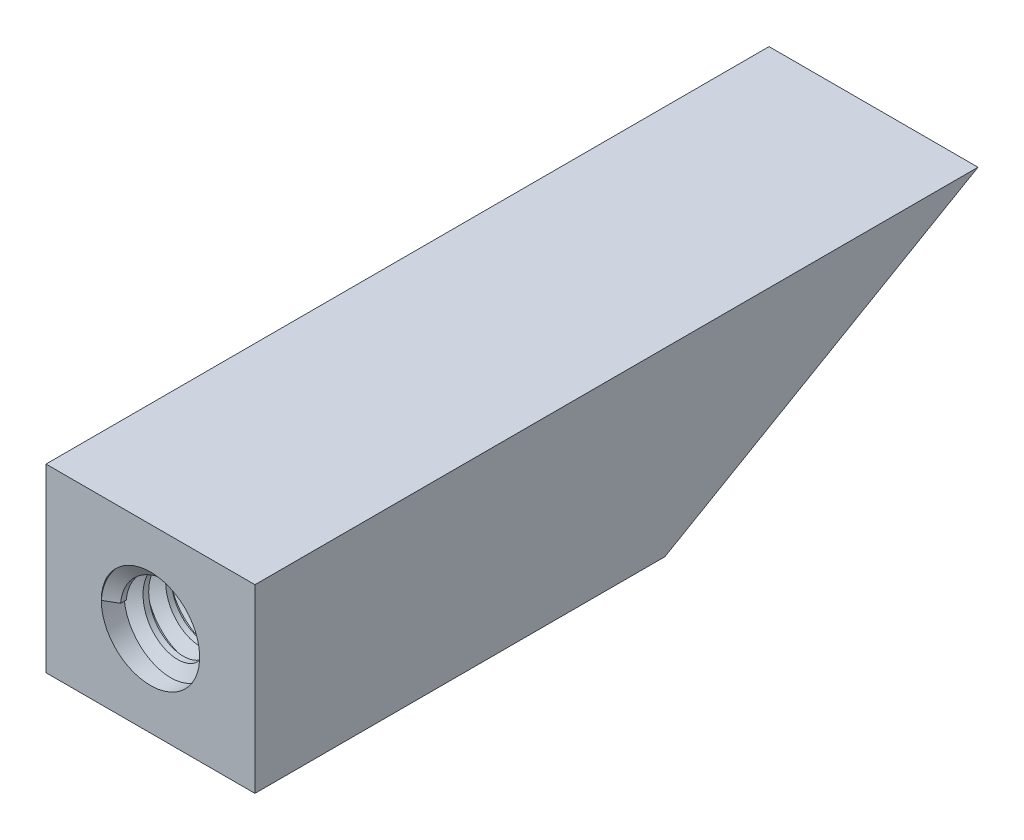
SolidWorks part; units mm, degrees
ref_plane "Front Plane" through (0, 0, 0) normal (0, 0, 1) x (1, 0, 0)
ref_plane "Top Plane" through (0, 0, 0) normal (0, 1, 0) x (1, 0, 0)
ref_plane "Right Plane" through (0, 0, 0) normal (1, 0, 0) x (0, 0, -1)
sketch "Sketch1" plane through (0, 0, 0) normal (0, 0, 1) x (1, 0, 0)
  line L1 (-3.6703, -3.175) -> (3.6703, -3.175)
  line L2 (-3.6703, -3.175) -> (-3.6703, 3.175)
  line L3 (-3.6703, 3.175) -> (3.6703, 3.175)
  line L4 (3.6703, -3.175) -> (3.6703, 3.175)
  line L5 (-3.6703, -3.175) -> (3.6703, 3.175) construction
  line L6 (-3.6703, 3.175) -> (3.6703, -3.175) construction
  point P0 (0, 0)
  dimension "D1" = 6.35
  dimension "D2" = 7.3406
extrude "Boss-Extrude1" add sketch "Sketch1" along normal blind 25.4
sketch "Sketch3" plane through (0, 0, 25.4) normal (0, 0, 1) x (1, 0, 0)
  line L0 (-3.6703, 3.175) -> (3.6703, -3.175) construction
  circle A0 centre (0, 0) radius 1.7272
  dimension "D1" = 3.4544
extrude "Cut-Extrude2" cut sketch "Sketch3" against normal blind 25.4
thread "Thread1" pitch 0.7937 method extrude profile "Thread Profile3" start angle 0, offset 0, length 25.4, pitch 0.7937, diameter 3.4544
ref_plane "Plane3" through (-1.7272, 0, 25.4) normal (0, -1, 0) x (-1, 0, 0)
sketch "Thread Profile3" plane through (-1.7272, 0, 25.4) normal (0, -1, 0) x (-1, 0, 0)
  line L0 (0, 0) -> (0, 0.7937) construction
  line L11 (0, 0) -> (0, 0.6945)
  line L12 (0, 0.6945) -> (-0.4296, 0.4465)
  line L13 (-0.4296, 0.4465) -> (-0.4296, 0.248)
  line L15 (-0.4296, 0.248) -> (0, 0)
  line L17 (-0.4296, 0.3473) -> (0, 0.3473) construction
  point P2 (0, 0)
  dimension "Pitch" = 0.7937
  dimension "Profile_Angle" = 60
  dimension "Profile_Land" = 0.1984
  dimension "Profile_Height" = 0.4296
sketch "Sketch2" plane through (3.6703, 0, 0) normal (1, 0, 0) x (0, 0, -1)
  line L0 (0, 3.175) -> (-10.9985, -3.175)
  line L1 (-25.4, -3.175) -> (0, -3.175) construction
  line L2 (-10.9985, -3.175) -> (0, -3.175)
  line L3 (0, -3.175) -> (0, 3.175)
  line L4 (0, 3.175) -> (0, -3.175)
  line L5 (0, 3.175) -> (2.54, 3.175)
  line L6 (0, -3.175) -> (2.54, -3.175)
  line L7 (2.54, 3.175) -> (2.54, -3.175)
  point P5 (0, 0)
  line M3 (0, -3.175) -> (0, 3.175)
  line M6 (-25.4, -3.175) -> (0, -3.175)
  dimension "D1" = 30
  dimension "D2" = 2.54
extrude "Cut-Extrude3" cut sketch "Sketch2" against normal blind 7.3406 and the other way through all contours L0 M3 M6 | L7 L5 L6 M3 region at (3.6703, -1.0583, 3.6662) region at (3.6703, 0, -1.27)
